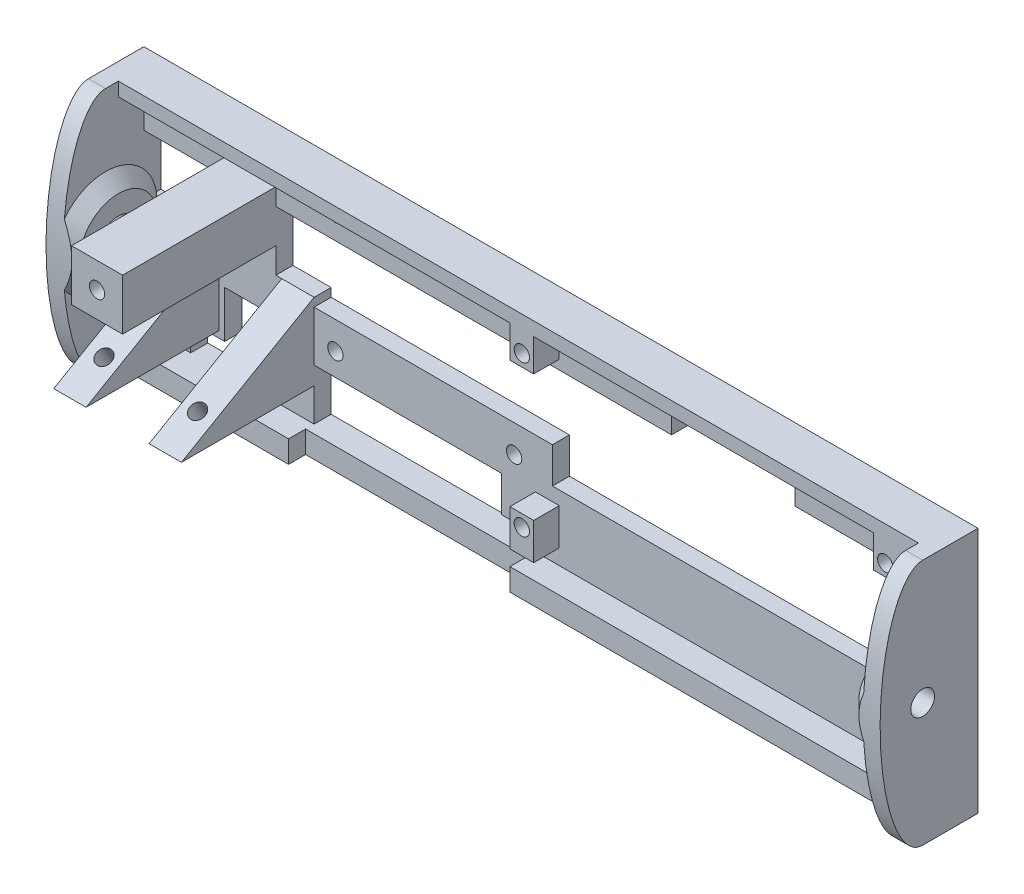
SolidWorks part; units mm, degrees
material "PET 90%"
ref_plane "Front Plane" through (0, 0, 0) normal (0, 0, 1) x (1, 0, 0)
ref_plane "Top Plane" through (0, 0, 0) normal (0, 1, 0) x (1, 0, 0)
ref_plane "Right Plane" through (0, 0, 0) normal (1, 0, 0) x (0, 0, -1)
sketch "Master" plane through (0, 0, 0) normal (0, 0, 1) x (1, 0, 0)
  line L0 (-35, 14.5) -> (-35, -14.5)
  line L1 (-33, 14.5) -> (61, 14.5)
  line L2 (-33, 14.5) -> (-33, -14.5)
  line L3 (-33, -14.5) -> (61, -14.5)
  line L4 (61, 14.5) -> (61, -14.5)
  line L5 (0, -14.5) -> (0, 14.5) construction
  line L6 (-33, 0) -> (-28, 0) construction
  line L7 (63, 14.5) -> (63, -14.5)
  line L8 (-35, 14.5) -> (-33, 14.5)
  line L9 (61, 14.5) -> (63, 14.5)
  line L10 (63, -14.5) -> (61, -14.5)
  line L11 (-33, -14.5) -> (-35, -14.5)
  line L12 (-33, -11.9) -> (61, -11.9)
  line L13 (-33, 12.9) -> (61, 12.9)
  line L14 (-13, -5.9) -> (-13, -11.9)
  line L15 (61, 8) -> (43.5, 8)
  line L16 (-33, -3.25) -> (-18.5, -3.25) construction
  line L17 (10.5, 12.9) -> (10.5, -10.1) construction
  line L18 (-10.5, 12.9) -> (-10.5, -5.9) construction
  line L19 (9, -10.1) -> (14, -10.1)
  line L20 (-28, 14.5) -> (-28, -14.5) construction
  line L21 (-23.5, 8) -> (-23.5, 1)
  line L22 (-17.5, 8) -> (-17.5, 1)
  line L23 (-23.5, 7) -> (-17.5, 7) construction
  line L24 (-20.5, 12.9) -> (-20.5, -3.25) construction
  line L25 (59.5, 12.9) -> (59.5, -10.1) construction
  line L26 (-33, -0.5) -> (-13, -0.5) construction
  line L27 (9, -5.9) -> (9, -10.1)
  line L28 (9, -10.1) -> (61, -10.1) construction
  line L29 (15, 0) -> (15, -4.2)
  line L30 (15, -4.2) -> (61, -4.2)
  line L31 (-27.5, -8.75) -> (-27.5, -11.9)
  line L32 (-18.5, -3.25) -> (-18.5, -11.9)
  line L33 (-17.5, 1) -> (-13, 1)
  line L34 (-13, -5.9) -> (9, -5.9)
  line L35 (-13, 1) -> (-13, 0)
  line L36 (-23.5, -3.25) -> (-18.5, -3.25)
  line L37 (-13, 0) -> (15, 0)
  line L38 (-23.5, 8) -> (-33, 8)
  line L39 (-13, 12.9) -> (-13, -5.9) construction
  line L40 (-23.5, 1) -> (-33, 1)
  line L41 (13, 12.9) -> (13, -11.9) construction
  line L42 (14, -10.1) -> (14, -11.9)
  line L43 (29, 8) -> (29, 11.9)
  line L44 (43.5, 8) -> (43.5, 11.9)
  line L45 (29, 8) -> (-17.5, 8)
  line L46 (29, 11.9) -> (43.5, 11.9)
  line L47 (-27.5, -8.75) -> (-23.5, -8.75)
  line L48 (-23.5, -8.75) -> (-23.5, -3.25)
  circle A8 centre (-20.5, 7) radius 0.9
  point P0 (0, 0)
  point P25 (10.5, -3.25)
  point P28 (-10.5, -3.25)
  point P41 (0, 0)
  point P42 (0, 0)
  dimension "D21" = 1.8
  dimension "D2" = 29
  dimension "D6" = 11.25
  dimension "D9" = 21
  dimension "D13" = 2.6
  dimension "D3" = 2
  dimension "D14" = 2
  dimension "D7" = 10.5
  dimension "D5" = 4.9
  dimension "D12" = 5.9
  dimension "D18" = 1.9
  dimension "D19" = 6
  dimension "D25" = 26
  dimension "D11" = 5
  dimension "D15" = 15
  dimension "D22" = 6
  dimension "D16" = 2
  dimension "D20" = 46.5
  dimension "D4" = 1.5
  dimension "D24" = 7.5
  dimension "D27" = 5.5
  dimension "D17" = 5.5
  dimension "D26" = 5.9
  dimension "D23" = 15
  dimension "D28" = 7
  dimension "D8" = 16
  dimension "D10" = 16
  dimension "D29" = 1
  dimension "D30" = 1.6
  dimension "D31" = 5.5
extrude "Boss-Extrude1" add sketch "Master" along normal blind 2 contours L2 L4 L13 region at (10.77, -0.0727, 0)
sketch "Sketch24" plane through (-57.48, -14.1, 2) normal (0, 0, 1) x (1, 0, 0)
  line L1 (44.98, 2.85) -> (69.98, 2.85) construction
  line L3 (44.98, 10.85) -> (44.98, 2.85) construction
  line L5 (44.98, 24.85) -> (44.98, 10.85) construction
  line L7 (44.98, 26.85) -> (44.98, 24.85) construction
  line L9 (46.98, 26.85) -> (44.98, 26.85) construction
  line L11 (67.98, 26.85) -> (46.98, 26.85) construction
  line L13 (69.98, 26.85) -> (67.98, 26.85) construction
  line L15 (69.98, 24.85) -> (69.98, 26.85) construction
  line L17 (69.98, 10.85) -> (69.98, 24.85) construction
  line L19 (69.98, 2.85) -> (69.98, 10.85) construction
  circle A1 centre (46.98, 10.85) radius 0.9
  circle A3 centre (46.98, 24.85) radius 0.9
  circle A5 centre (67.98, 24.85) radius 0.9
  circle A7 centre (67.98, 10.85) radius 0.9
  dimension "D1" = 1.8
extrude "Cut-Extrude8" cut sketch "Sketch24" against normal up to next
sketch "Sketch2" plane through (0, 0, 0) normal (0, 0, 1) x (1, 0, 0)
  line L0 (-35, 14.5) -> (-35, -14.5)
  line L1 (-33, 14.5) -> (61, 14.5)
  line L2 (-33, 14.5) -> (-33, -14.5)
  line L3 (-33, -14.5) -> (61, -14.5)
  line L4 (61, 14.5) -> (61, -14.5)
  line L5 (0, -14.5) -> (0, 14.5) construction
  line L6 (-33, 0) -> (-28, 0) construction
  line L7 (63, 14.5) -> (63, -14.5)
  line L8 (-35, 14.5) -> (-33, 14.5)
  line L9 (61, 14.5) -> (63, 14.5)
  line L10 (63, -14.5) -> (61, -14.5)
  line L11 (-33, -14.5) -> (-35, -14.5)
  line L12 (-33, -11.9) -> (61, -11.9)
  line L13 (-33, 12.9) -> (61, 12.9)
  line L14 (-13, -5.9) -> (-13, -11.9)
  line L15 (61, 8) -> (43.5, 8)
  line L16 (-33, -3.25) -> (-18.5, -3.25) construction
  line L17 (10.5, 12.9) -> (10.5, -10.1) construction
  line L18 (-10.5, 12.9) -> (-10.5, -5.9) construction
  line L19 (9, -10.1) -> (14, -10.1)
  line L20 (-28, 14.5) -> (-28, -14.5) construction
  line L21 (-23.5, 8) -> (-23.5, 1)
  line L22 (-17.5, 8) -> (-17.5, 1)
  line L23 (-23.5, 7) -> (-17.5, 7) construction
  line L24 (-20.5, 12.9) -> (-20.5, -3.25) construction
  line L25 (59.5, 12.9) -> (59.5, -10.1) construction
  line L26 (-33, -0.5) -> (-13, -0.5) construction
  line L27 (9, -5.9) -> (9, -10.1)
  line L28 (9, -10.1) -> (61, -10.1) construction
  line L29 (15, 0) -> (15, -4.2)
  line L30 (15, -4.2) -> (61, -4.2)
  line L31 (-27.5, -8.75) -> (-27.5, -11.9)
  line L32 (-18.5, -3.25) -> (-18.5, -11.9)
  line L33 (-17.5, 1) -> (-13, 1)
  line L34 (-13, -5.9) -> (9, -5.9)
  line L35 (-13, 1) -> (-13, 0)
  line L36 (-23.5, -3.25) -> (-18.5, -3.25)
  line L37 (-13, 0) -> (15, 0)
  line L38 (-23.5, 8) -> (-33, 8)
  line L39 (-13, 12.9) -> (-13, -5.9) construction
  line L40 (-23.5, 1) -> (-33, 1)
  line L41 (13, 12.9) -> (13, -11.9) construction
  line L42 (14, -10.1) -> (14, -11.9)
  line L43 (29, 8) -> (29, 11.9)
  line L44 (43.5, 8) -> (43.5, 11.9)
  line L45 (29, 8) -> (-17.5, 8)
  line L46 (29, 11.9) -> (43.5, 11.9)
  line L47 (-27.5, -8.75) -> (-23.5, -8.75)
  line L48 (-23.5, -8.75) -> (-23.5, -3.25)
  circle A8 centre (-20.5, 7) radius 0.9
  point P0 (0, 0)
  point P25 (10.5, -3.25)
  point P28 (-10.5, -3.25)
extrude "Boss-Extrude2" add sketch "Sketch2" along normal blind 5 contours L12 L2 L3 L4 | L2 L13 L4 L1 region at (14, 13.7, 0) region at (14, -13.2, 0)
sketch "Sketch3" plane through (0, 0, 0) normal (0, 0, 1) x (1, 0, 0)
  line L0 (-35, 14.5) -> (-35, -14.5)
  line L1 (-33, 14.5) -> (61, 14.5)
  line L2 (-33, 14.5) -> (-33, -14.5)
  line L3 (-33, -14.5) -> (61, -14.5)
  line L4 (61, 14.5) -> (61, -14.5)
  line L5 (0, -14.5) -> (0, 14.5) construction
  line L6 (-33, 0) -> (-28, 0) construction
  line L7 (63, 14.5) -> (63, -14.5)
  line L8 (-35, 14.5) -> (-33, 14.5)
  line L9 (61, 14.5) -> (63, 14.5)
  line L10 (63, -14.5) -> (61, -14.5)
  line L11 (-33, -14.5) -> (-35, -14.5)
  line L12 (-33, -11.9) -> (61, -11.9)
  line L13 (-33, 12.9) -> (61, 12.9)
  line L14 (-13, -5.9) -> (-13, -11.9)
  line L15 (61, 8) -> (43.5, 8)
  line L16 (-33, -3.25) -> (-18.5, -3.25) construction
  line L17 (10.5, 12.9) -> (10.5, -10.1) construction
  line L18 (-10.5, 12.9) -> (-10.5, -5.9) construction
  line L19 (9, -10.1) -> (14, -10.1)
  line L20 (-28, 14.5) -> (-28, -14.5) construction
  line L21 (-23.5, 8) -> (-23.5, 1)
  line L22 (-17.5, 8) -> (-17.5, 1)
  line L23 (-23.5, 7) -> (-17.5, 7) construction
  line L24 (-20.5, 12.9) -> (-20.5, -3.25) construction
  line L25 (59.5, 12.9) -> (59.5, -10.1) construction
  line L26 (-33, -0.5) -> (-13, -0.5) construction
  line L27 (9, -5.9) -> (9, -10.1)
  line L28 (9, -10.1) -> (61, -10.1) construction
  line L29 (15, 0) -> (15, -4.2)
  line L30 (15, -4.2) -> (61, -4.2)
  line L31 (-27.5, -8.75) -> (-27.5, -11.9)
  line L32 (-18.5, -3.25) -> (-18.5, -11.9)
  line L33 (-17.5, 1) -> (-13, 1)
  line L34 (-13, -5.9) -> (9, -5.9)
  line L35 (-13, 1) -> (-13, 0)
  line L36 (-23.5, -3.25) -> (-18.5, -3.25)
  line L37 (-13, 0) -> (15, 0)
  line L38 (-23.5, 8) -> (-33, 8)
  line L39 (-13, 12.9) -> (-13, -5.9) construction
  line L40 (-23.5, 1) -> (-33, 1)
  line L41 (13, 12.9) -> (13, -11.9) construction
  line L42 (14, -10.1) -> (14, -11.9)
  line L43 (29, 8) -> (29, 11.9)
  line L44 (43.5, 8) -> (43.5, 11.9)
  line L45 (29, 8) -> (-17.5, 8)
  line L46 (29, 11.9) -> (43.5, 11.9)
  line L47 (-27.5, -8.75) -> (-23.5, -8.75)
  line L48 (-23.5, -8.75) -> (-23.5, -3.25)
  circle A8 centre (-20.5, 7) radius 0.9
  point P0 (0, 0)
  point P25 (10.5, -3.25)
  point P28 (-10.5, -3.25)
extrude "Boss-Extrude3" add sketch "Sketch3" along normal blind 6.5 contours L11 L2 L8 L0 | L10 L7 L9 L4 region at (-34, 0, 0) region at (62, 0, 0)
sketch "Sketch6" plane through (-35, 0, 0) normal (-1, 0, 0) x (0, 0, 1)
  line L4 (0, 0) -> (6.5, 0) construction
  line L5 (6.5, 14.5) -> (6.5, -14.5) construction
  line L6 (6.5, 14.5) -> (0, 14.5) construction
  line L7 (6.5, -14.5) -> (0, -14.5) construction
  circle A0 centre (6.5, 0) radius 3.55
  circle A1 centre (6.5, 10.5) radius 1.1
  circle A2 centre (6.5, -10.5) radius 1.1
  ellipse E0 centre (6.5, 0) end of major axis (6.5, 14.5) minor radius 5
  line M3 (6.5, -14.5) -> (6.5, 14.5)
  dimension "D1" = 7.1
  dimension "D3" = 2.2
  dimension "D2" = 10
  dimension "D4" = 21
extrude "Boss-Extrude4" add sketch "Sketch6" against normal blind 2 contours E0 A1 A0 A2 M3 | A2 | A0 M3 | A1 region at (-35, 0, 8.0067) region at (-35, 2.7183, 9.2183) region at (-35, 10.5, 6.9669) region at (-35, -10.5, 6.9669)
sketch "Sketch7" plane through (63, 0, 0) normal (-1, 0, 0) x (0, 0, 1)
  line L4 (0, 0) -> (6.5, 0) construction
  circle A0 centre (6.5, 0) radius 3.55
  circle A1 centre (6.5, 10.5) radius 1.1
  circle A2 centre (6.5, -10.5) radius 1.1
  ellipse E0 centre (6.5, 0) end of major axis (6.5, 14.5) minor radius 5
  line M16 (6.5, 14.5) -> (6.5, -14.5)
extrude "Boss-Extrude5" add sketch "Sketch7" along normal blind 2 contours E0 A2 A0 A1 M16 | A2 | A0 M16 | A1 region at (63, 0, 8.0067) region at (63, 2.7183, 9.2183) region at (63, 10.5, 6.9669) region at (63, -10.5, 6.9669)
sketch "Sketch9" plane through (0, 0, 0) normal (-1, 0, 0) x (0, 0, 1)
  line L4 (0, 0) -> (6.5, 0) construction
  circle A0 centre (6.5, 0) radius 3.55
  circle A1 centre (6.5, 10.5) radius 1.1
  circle A2 centre (6.5, -10.5) radius 1.1
  ellipse E0 centre (6.5, 0) end of major axis (6.5, 14.5) minor radius 5
sketch "Sketch8" plane through (-35, 0, 0) normal (-1, 0, 0) x (0, 0, 1)
  circle A0 centre (6.5, 0) radius 2.275
  dimension "D1" = 4.55
extrude "Servo holes" cut sketch "Sketch8" against normal up to next and the other way through all contours A0
sketch "Sketch10" plane through (0, 0, 2) normal (0, 0, 1) x (1, 0, 0)
  line L0 (-17.5, 8) -> (-17.5, 1) construction
  line L1 (-23.5, 4) -> (-17.5, 4)
  line L2 (-23.5, 4) -> (-23.5, 10)
  line L3 (-23.5, 10) -> (-17.5, 10)
  line L4 (-17.5, 4) -> (-17.5, 10)
  line L5 (-23.5, 4) -> (-17.5, 10) construction
  line L6 (-23.5, 10) -> (-17.5, 4) construction
  circle A0 centre (-20.5, 7) radius 0.9 construction
  circle A1 centre (-20.5, 7) radius 0.9
extrude "Boss-Extrude6" add sketch "Sketch10" along normal blind 18
sketch "HC-SR04" plane through (-57.48, -14.1, 2) normal (0, 0, 1) x (1, 0, 0)
  line L0 (24.48, 27) -> (118.48, 27) construction
  line L1 (115.98, 26) -> (70.48, 26) construction
  line L2 (73.28, 23.2) -> (70.48, 23.2)
  line L3 (70.48, 26) -> (70.48, 5.5) construction
  line L4 (73.28, 23.2) -> (73.28, 26)
  line L5 (70.48, 5.5) -> (115.98, 5.5) construction
  line L7 (115.98, 5.5) -> (115.98, 26) construction
  line L9 (73.28, 23.2) -> (70.48, 26) construction
  line L10 (73.28, 26) -> (70.48, 23.2) construction
  line L11 (73.28, 8.3) -> (70.48, 8.3)
  line L12 (73.28, 8.3) -> (73.28, 5.5)
  line L15 (73.28, 8.3) -> (70.48, 5.5) construction
  line L16 (73.28, 5.5) -> (70.48, 8.3) construction
  line L17 (113.18, 8.3) -> (115.98, 8.3)
  line L18 (113.18, 8.3) -> (113.18, 5.5)
  line L21 (113.18, 8.3) -> (115.98, 5.5) construction
  line L22 (113.18, 5.5) -> (115.98, 8.3) construction
  line L23 (113.18, 23.2) -> (115.98, 23.2)
  line L24 (113.18, 23.2) -> (113.18, 26)
  line L27 (113.18, 23.2) -> (115.98, 26) construction
  line L28 (113.18, 26) -> (115.98, 23.2) construction
  line L29 (70.48, 27) -> (73.28, 27)
  line L30 (71.48, 2.2) -> (118.48, 2.2) construction
  line L31 (113.18, 2.2) -> (118.48, 2.2)
  line L32 (113.18, 26) -> (113.18, 27)
  line L33 (118.48, 27) -> (118.48, 22.1) construction
  line L34 (118.48, 27) -> (118.48, 23.2)
  line L35 (115.98, 23.2) -> (118.48, 23.2)
  line L36 (115.98, 8.3) -> (118.48, 8.3)
  line L37 (118.48, 9.9) -> (118.48, 2.2) construction
  line L38 (118.48, 8.3) -> (118.48, 2.2)
  line L39 (113.18, 5.5) -> (113.18, 2.2)
  line L40 (73.28, 26) -> (73.28, 27)
  line L41 (73.28, 5.5) -> (73.28, 4)
  line L42 (70.48, 8.3) -> (70.48, 4)
  line L43 (66.48, 4) -> (71.48, 4) construction
  line L44 (70.48, 4) -> (73.28, 4)
  line L45 (70.48, 23.2) -> (70.48, 27)
  line L46 (113.18, 27) -> (118.48, 27)
  arc A1 (71.88, 23.625) -> (71.88, 25.575) centre (71.88, 24.6) ccw construction
  arc A3 (71.88, 25.575) -> (71.88, 23.625) centre (71.88, 24.6) ccw construction
  arc A5 (71.88, 5.925) -> (71.88, 7.875) centre (71.88, 6.9) ccw construction
  arc A7 (71.88, 7.875) -> (71.88, 5.925) centre (71.88, 6.9) ccw construction
  arc A9 (114.58, 7.875) -> (114.58, 5.925) centre (114.58, 6.9) ccw construction
  arc A11 (114.58, 5.925) -> (114.58, 7.875) centre (114.58, 6.9) ccw construction
  arc A13 (114.58, 23.625) -> (114.58, 25.575) centre (114.58, 24.6) ccw construction
  arc A15 (114.58, 25.575) -> (114.58, 23.625) centre (114.58, 24.6) ccw construction
ref_plane "Laser Pointer Boss Left" through (-28, 0, 0) normal (1, 0, 0) x (0, 0, -1)
sketch "Laser Pointer Boss" plane through (-28, 0, 0) normal (1, 0, 0) x (0, 0, -1)
  line L0 (0, 14.5) -> (0, -14.5) construction
  line L1 (0, 14.5) -> (0, -14.5) construction
  line L6 (-2, 1) -> (-2, -11.9) construction
  line L14 (-2, 1) -> (-2, -8)
  line L15 (-2, -8) -> (-17.5885, -8)
  line L16 (-17.5885, -8) -> (-2, 1)
  dimension "D1" = 30
  dimension "D2" = 18
extrude "Boss-Extrude10" add sketch "Laser Pointer Boss" along normal blind 3.8 contours L16 L15 L14 region at (-28, -5, 7.1962)
ref_plane "Laser Pointer Boss Right" through (-13, 0, 0) normal (1, 0, 0) x (0, 0, -1)
sketch "Sketch22" plane through (-13, 0, 0) normal (1, 0, 0) x (0, 0, -1)
  line L1 (0, 14.5) -> (0, -14.5) construction
  line L14 (-2, 1) -> (-2, -8)
  line L15 (-2, -8) -> (-17.5885, -8)
  line L16 (-17.5885, -8) -> (-2, 1)
extrude "Boss-Extrude11" add sketch "Sketch22" against normal blind 3.8
sketch "Laser Pointer Mounting Holes" plane through (-57.48, -0.1336, 3.9635) normal (0, 0.866, 0.5) x (1, 0, 0)
  line L0 (44.48, 2.2672) -> (44.48, -15.7328) construction
  line L1 (44.48, 2.2672) -> (44.48, -15.7328) construction
  line L2 (29.48, -15.7328) -> (29.48, 2.2672) construction
  line L3 (29.48, -15.7328) -> (29.48, 2.2672) construction
  line L4 (33.28, -15.7328) -> (29.48, -15.7328) construction
  line L5 (33.28, -15.7328) -> (29.48, -15.7328) construction
  line L6 (31.48, -11.2328) -> (42.48, -11.2328) construction
  circle A1 centre (31.48, -11.2328) radius 0.9
  circle A3 centre (42.48, -11.2328) radius 0.9
  point P10 (31.38, -15.7328)
  dimension "D1" = 1.8
  dimension "D2" = 2
  dimension "D3" = 2
  dimension "D4" = 4.5011
extrude "Cut-Extrude6" cut sketch "Laser Pointer Mounting Holes" against normal up to next
extrude "Boss-Extrude12" add sketch "HC-SR04" along normal blind 3
sketch "Sketch23" plane through (0, 0, 5) normal (0, 0, 1) x (1, 0, 0)
  circle A4 centre (14.4, 10.5) radius 0.9
  circle A5 centre (14.4, -7.2) radius 0.9
  circle A6 centre (57.1, -7.2) radius 0.9
  circle A7 centre (57.1, 10.5) radius 0.9
  dimension "D1" = 1.8
extrude "Cut-Extrude7" cut sketch "Sketch23" against normal up to next
sketch "Sketch25" plane through (63, 0, 0) normal (1, 0, 0) x (0, 0, -1)
  circle A0 centre (-6.5, 0) radius 3.55 construction
  circle A1 centre (-6.5, 0) radius 3.55 construction
  circle A2 centre (-6.5, 0) radius 1.4
  dimension "D1" = 2.8
extrude "Cut-Extrude9" cut sketch "Sketch25" against normal up to next
sketch "Sketch26" plane through (-33, 0, 0) normal (1, 0, 0) x (0, 0, -1)
  circle A0 centre (-6.5, 0) radius 4.55
  circle A1 centre (-6.5, 0) radius 2.275 construction
  circle A2 centre (-6.5, 0) radius 2.275
  dimension "D1" = 9.1
extrude "Boss-Extrude13" add sketch "Sketch26" along normal blind 1.5
chamfer "Chamfer1" distance 1.5 angle 45 1 edges at (-33, 0, 11.05)
sketch "Sketch27" plane through (61, 0, 0) normal (-1, 0, 0) x (0, 0, 1)
  circle A0 centre (6.5, 0) radius 1.4 construction
  circle A1 centre (6.5, 0) radius 1.4
  circle A2 centre (6.5, 0) radius 3.5
  dimension "D1" = 7
extrude "Boss-Extrude14" add sketch "Sketch27" along normal blind 2
chamfer "Chamfer2" distance 2 angle 45 1 edges at (61, 0, 3)
sketch "Sketch29" plane through (0, -14.5, 0) normal (0, -1, 0) x (1, 0, 0)
  line L2 (-13, 3) -> (13, 3)
  line L7 (-13, 5) -> (13, 5)
  line L10 (-13, 3) -> (-13, 5)
  line L16 (13, 5) -> (13, 2) construction
  line L20 (13, 3) -> (13, 2) construction
  line L21 (13, 3) -> (13, 5)
  line L22 (-13, 2) -> (-13, 0) construction
  line L23 (-13, 2) -> (-13, 0) construction
  dimension "D1" = 2
extrude "FPC" cut sketch "Sketch29" against normal up to next
equation "\"side_thickness\"= 2"
equation "\"D3@Master\"=\"side_thickness\""
equation "\"D1@Boss-Extrude4\"=\"side_thickness\""
equation "\"D1@Boss-Extrude5\"=\"side_thickness\""
equation "\"D14@Master\"=\"side_thickness\""
